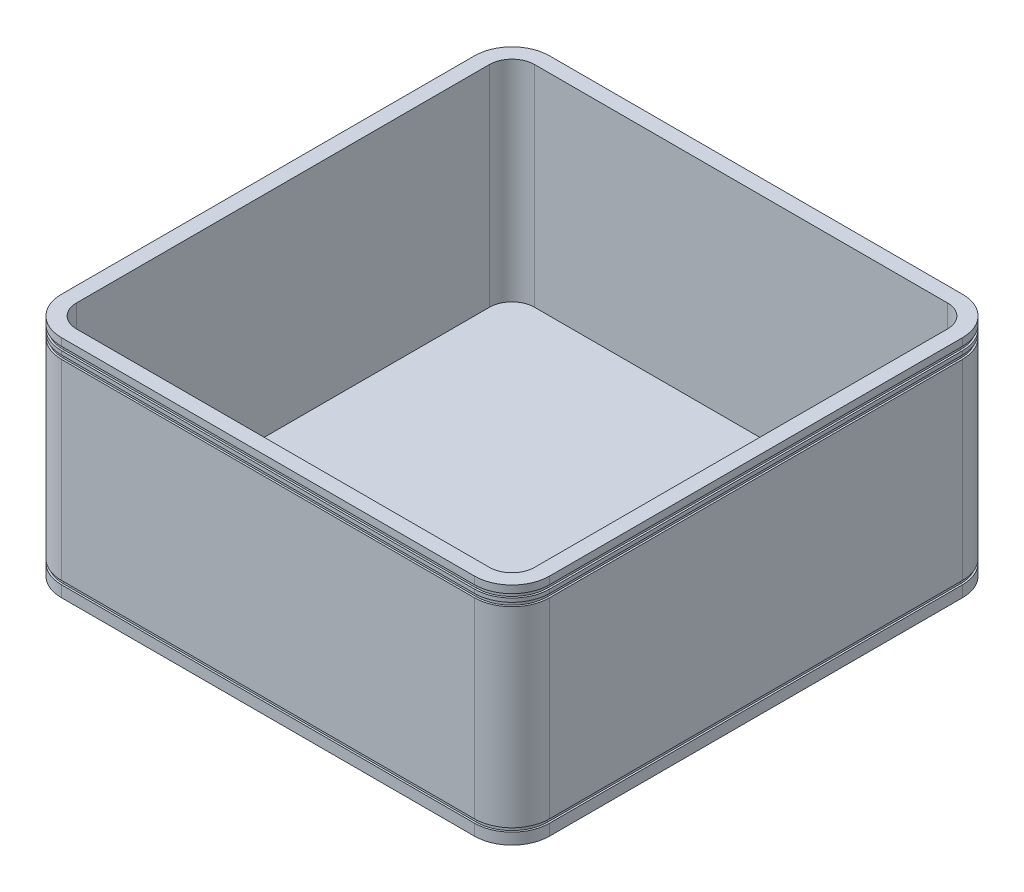
SolidWorks part; units mm, degrees
ref_plane "Alzado" through (0, 0, 0) normal (0, 0, 1) x (1, 0, 0)
ref_plane "Planta" through (0, 0, 0) normal (0, 1, 0) x (1, 0, 0)
ref_plane "Vista lateral" through (0, 0, 0) normal (1, 0, 0) x (0, 0, -1)
sketch "Croquis1" plane through (0, 0, 0) normal (0, 1, 0) x (1, 0, 0)
  line L1 (65, 65) -> (-65, 65)
  line L2 (65, 65) -> (65, -65)
  line L3 (65, -65) -> (-65, -65)
  line L4 (-65, 65) -> (-65, -65)
  line L5 (65, 65) -> (-65, -65) construction
  line L6 (65, -65) -> (-65, 65) construction
  point P0 (0, 0)
  dimension "D1" = 130
  dimension "D2" = 130
extrude "Saliente-Extruir1" add sketch "Croquis1" along normal blind 60
fillet "Redondeo1" radius 10 4 edges at (-65, 30, -65) (65, 30, -65) (65, 30, 65) (-65, 30, 65)
shell "Vaciado1" thickness 4 removed face at (0, 60, 0)
ref_plane "Plano1" through (0, 58, 0) normal (0, 1, 0) x (1, 0, 0)
ref_plane "Plano2" through (0, 56, 0) normal (0, 1, 0) x (1, 0, 0)
ref_plane "Plano3" through (0, 3, 0) normal (0, -1, 0) x (-1, 0, 0)
sketch "Croquis2" plane through (0, 0, 0) normal (0, -1, 0) x (1, 0, 0)
  line L0 (55, -65) -> (-55, -65) construction
  line L1 (65, 55) -> (65, -55) construction
  line L2 (-55, 65) -> (55, 65) construction
  line L3 (-65, -55) -> (-65, 55) construction
  line L4 (55, -65) -> (-55, -65)
  line L5 (65, 55) -> (65, -55)
  line L6 (-55, 65) -> (55, 65)
  line L7 (-65, -55) -> (-65, 55)
  line L8 (55, -64.5) -> (-55, -64.5)
  line L9 (64.5, 55) -> (64.5, -55)
  line L10 (-55, 64.5) -> (55, 64.5)
  line L11 (-64.5, -55) -> (-64.5, 55)
  arc A0 (-55, 65) -> (-65, 55) centre (-55, 55) ccw construction
  arc A1 (-65, -55) -> (-55, -65) centre (-55, -55) ccw construction
  arc A2 (55, -65) -> (65, -55) centre (55, -55) ccw construction
  arc A3 (65, 55) -> (55, 65) centre (55, 55) ccw construction
  arc A4 (-65, -55) -> (-55, -65) centre (-55, -55) ccw
  arc A5 (55, -65) -> (65, -55) centre (55, -55) ccw
  arc A6 (65, 55) -> (55, 65) centre (55, 55) ccw
  arc A7 (-55, 65) -> (-65, 55) centre (-55, 55) ccw
  arc A8 (-64.5, -55) -> (-55, -64.5) centre (-55, -55) ccw
  arc A9 (55, -64.5) -> (64.5, -55) centre (55, -55) ccw
  arc A10 (64.5, 55) -> (55, 64.5) centre (55, 55) ccw
  arc A11 (-55, 64.5) -> (-64.5, 55) centre (-55, 55) ccw
  dimension "D1" = 0.5
extrude "Cortar-Extruir1" cut sketch "Croquis2" along normal blind 1 from surface starting at plane "Plano1"
extrude "Cortar-Extruir2" cut sketch "Croquis2<2>" along normal blind 1 from surface starting at plane "Plano2"
sketch "Croquis2<2>" plane through (0, 0, 0) normal (0, -1, 0) x (1, 0, 0) same geometry as "Croquis2"
extrude "Cortar-Extruir3" cut sketch "Croquis2<3>" against normal blind 1 from surface starting at plane "Plano3"
sketch "Croquis2<3>" plane through (0, 0, 0) normal (0, -1, 0) x (1, 0, 0) same geometry as "Croquis2"
